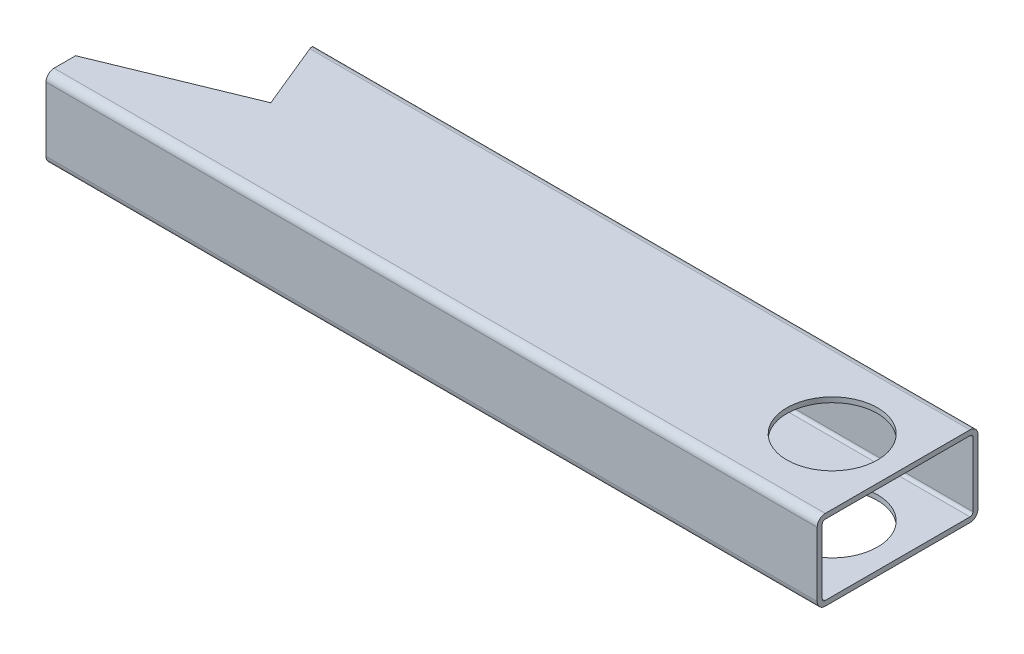
SolidWorks part; units mm, degrees
material "6061 Alloy"
ref_plane "Front" through (0, 0, 0) normal (0, 0, 1) x (1, 0, 0)
ref_plane "Top" through (0, 0, 0) normal (0, 1, 0) x (1, 0, 0)
ref_plane "Right" through (0, 0, 0) normal (1, 0, 0) x (0, 0, -1)
sketch "Sketch1" plane through (0, 0, 0) normal (1, 0, 0) x (0, 0, -1)
  line L1 (-2.54, 0) -> (-48.26, 0)
  line L2 (0, 2.54) -> (0, 22.86)
  line L3 (-2.54, 25.4) -> (-48.26, 25.4)
  line L4 (-50.8, 2.54) -> (-50.8, 22.86)
  arc A0 (-50.8, 2.54) -> (-48.26, 0) centre (-48.26, 2.54) ccw
  arc A1 (-2.54, 0) -> (0, 2.54) centre (-2.54, 2.54) ccw
  arc A2 (0, 22.86) -> (-2.54, 25.4) centre (-2.54, 22.86) ccw
  arc A3 (-48.26, 25.4) -> (-50.8, 22.86) centre (-48.26, 22.86) ccw
  point P7 (-50.8, 0)
  point P10 (0, 0)
  point P13 (0, 25.4)
  dimension "D3" = 2.54
  dimension "D1" = 25.4
  dimension "D2" = 50.8
extrude "Extrude-Thin1" add sketch "Sketch1" against normal blind 243.6368 thin thin type one direction reverse wall 1.5875
sketch "Sketch3" plane through (0, 25.4, 0) normal (0, 1, 0) x (1, 0, 0)
  line L0 (0, 49.2125) -> (79.6022, 243.0747)
  line L1 (0, -1.5875) -> (25.4, -1.5875)
  line L2 (0, -1.5875) -> (0, 49.2125)
  line L3 (0, 49.2125) -> (25.4, 49.2125)
  line L4 (25.4, -1.5875) -> (25.4, 49.2125)
  line L5 (79.6022, 243.0747) -> (126.5949, 223.7789)
  line L6 (126.5949, 223.7789) -> (34.0567, -1.5875)
  line L7 (71.7537, 223.9604) -> (118.7463, 204.6646) construction
  line L8 (95.25, 214.3125) -> (0, 214.3125)
  line L9 (0, 49.2125) -> (0, 289.0515)
  line L10 (25.4, -1.5875) -> (34.0567, -1.5875)
  circle A0 centre (95.25, 214.3125) radius 14.3129
  point P11 (95.25, 214.3125)
  dimension "D4" = 28.6258
  dimension "D5" = 6.35
  dimension "D1" = 25.4
  dimension "D2" = 50.8
  dimension "D3" = 50.8
  dimension "D6" = 95.25
  dimension "D7" = 165.1
  dimension "D8" = 243.6254
  dimension "D9" = 209.5687
sketch "Sketch4" plane through (0, 25.4, 0) normal (0, 1, 0) x (1, 0, 0)
  line L0 (-20.6629, -48.26) -> (-20.6629, -2.54) construction
  line L2 (-243.6368, -2.54) -> (0, -2.54) construction
  line L3 (-243.6368, -48.26) -> (0, -48.26) construction
  line L4 (0, -2.54) -> (0, -48.26) construction
  line L5 (0, 0) -> (-209.5754, 0) construction
  line L6 (-243.6368, 0) -> (0, 0) construction
  line L7 (-209.5754, 0) -> (-199.9249, -23.4953)
  line L8 (-199.9249, -23.4953) -> (-243.6368, -41.4496)
  line L10 (-243.6368, -48.26) -> (-243.6368, -50.8) construction
  line L11 (-209.5754, 0) -> (-243.6368, 0)
  line L12 (-243.6368, 0) -> (-243.6368, -41.4496)
  line L13 (-243.6368, -2.54) -> (-243.6368, -48.26) construction
  circle A0 centre (-20.6629, -25.4) radius 14.3129
  point P2 (-243.6368, -50.8)
  point P5 (-20.6629, -25.4)
  point P12 (-243.6368, -44.2423)
  point P23 (0, 0)
  dimension "D1" = 28.6258
  dimension "D2" = 6.35
  dimension "D3" = 25.4
  dimension "D4" = 209.5754
  dimension "D5" = 67.67
extrude "Cut-Extrude1" cut sketch "Sketch4" against normal through all and the other way through all
